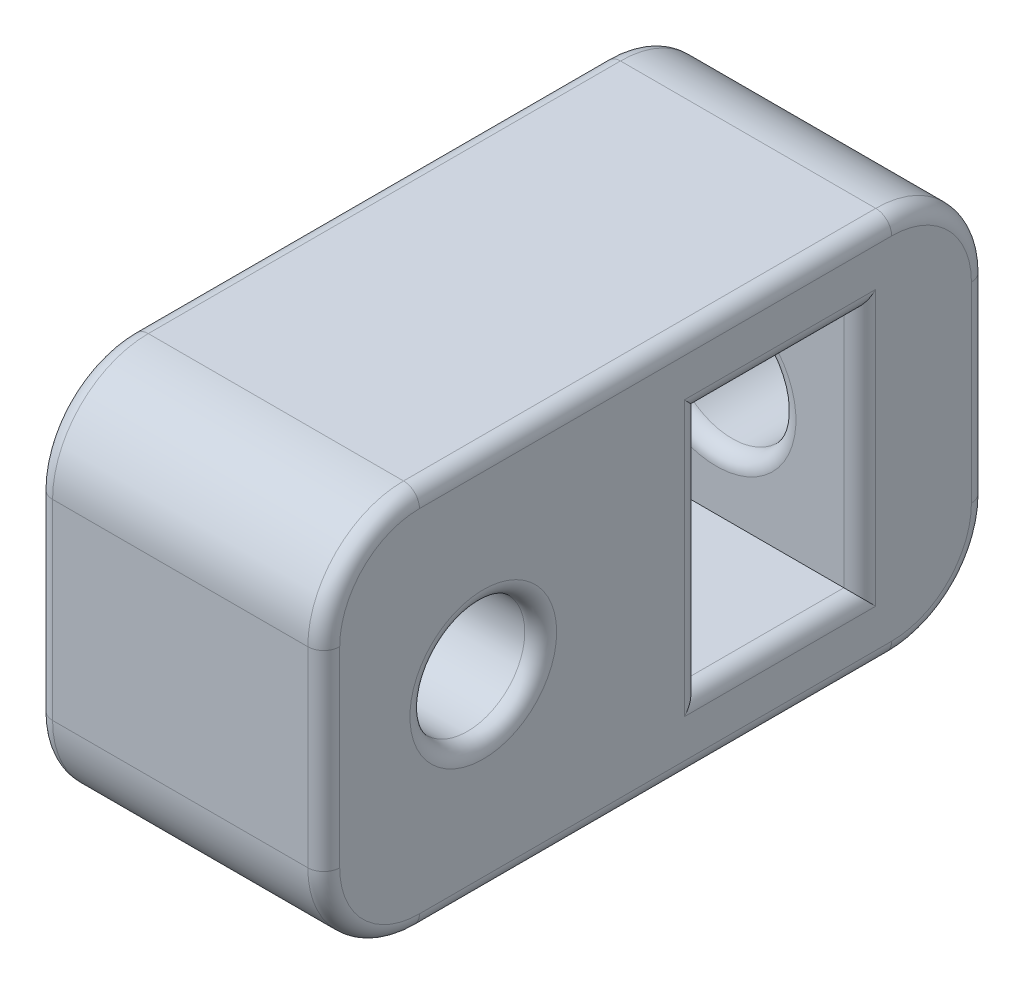
SolidWorks part; units mm, degrees
ref_plane "Front Plane" through (0, 0, 0) normal (0, 0, 1) x (1, 0, 0)
ref_plane "Top Plane" through (0, 0, 0) normal (0, 1, 0) x (1, 0, 0)
ref_plane "Right Plane" through (0, 0, 0) normal (1, 0, 0) x (0, 0, -1)
sketch "Sketch1" plane through (0, 0, 0) normal (1, 0, 0) x (0, 0, -1)
  line L1 (-6.35, 7.62) -> (20.066, 7.62)
  line L2 (-6.35, 7.62) -> (-6.35, -7.62)
  line L3 (-6.35, -7.62) -> (20.066, -7.62)
  line L4 (20.066, 7.62) -> (20.066, -7.62)
  circle A0 centre (0, 0) radius 2.286
  point P7 (2.286, 0)
  dimension "D2" = 4.572
  dimension "D1" = 7.62
  dimension "D3" = 15.24
  dimension "D4" = 6.35
  dimension "D5" = 17.78
extrude "Boss-Extrude1" add sketch "Sketch1" along normal mid plane 11.43
sketch "Sketch2" plane through (0, 0, -20.066) normal (0, 0, -1) x (-1, 0, 0)
  circle A0 centre (0, 0) radius 2.54
  dimension "D1" = 5.08
extrude "Cut-Extrude1" cut sketch "Sketch2" against normal blind 12.7
fillet "Fillet1" radius 3.81 4 edges at (0, -7.62, -20.066) (0, 7.62, -20.066) (0, 7.62, 6.35) (0, -7.62, 6.35)
sketch "Sketch3" plane through (5.715, 0, 0) normal (1, 0, 0) x (0, 0, -1)
  line L0 (20.066, -3.81) -> (20.066, 3.81) construction
  line L1 (14.986, -4.826) -> (8.636, -4.826)
  line L2 (14.986, -4.826) -> (14.986, 4.826)
  line L3 (14.986, 4.826) -> (8.636, 4.826)
  line L4 (8.636, -4.826) -> (8.636, 4.826)
  line L5 (14.986, -4.826) -> (8.636, 4.826) construction
  line L6 (14.986, 4.826) -> (8.636, -4.826) construction
  point P0 (11.811, 0)
  dimension "D1" = 6.35
  dimension "D2" = 5.08
  dimension "D3" = 9.652
extrude "Cut-Extrude2" cut sketch "Sketch3" against normal through all
fillet "Fillet2" radius 0.635 26 edges at (-5.715, 0, -2.286) (-5.715, 6.5041, -18.9501) (-5.715, 7.62, -6.858) (-5.715, 6.5041, 5.2341) (-5.715, 0, 6.35) (-5.715, -6.5041, 5.2341) (-5.715, -7.62, -6.858) (-5.715, -6.5041, -18.9501) (-5.715, 0, -20.066) (-5.715, 0, -14.986) (-5.715, -4.826, -11.811) (-5.715, 4.826, -11.811) (5.715, 0, -2.286) (5.715, -6.5041, 5.2341) (5.715, 0, 6.35) (5.715, 6.5041, 5.2341) (5.715, 7.62, -6.858) (5.715, 6.5041, -18.9501) (5.715, 0, -20.066) (5.715, -6.5041, -18.9501) (5.715, -7.62, -6.858) (5.715, -4.826, -11.811) (5.715, 0, -14.986) (5.715, 4.826, -11.811) (-5.715, 0, -8.636) (5.715, 0, -8.636)
fillet "Fillet3" radius 0.635 4 edges at (0, 2.54, -20.066) (-2.54, 0, -14.986) (0, 2.54, -7.366) (0, -2.54, -8.636)
